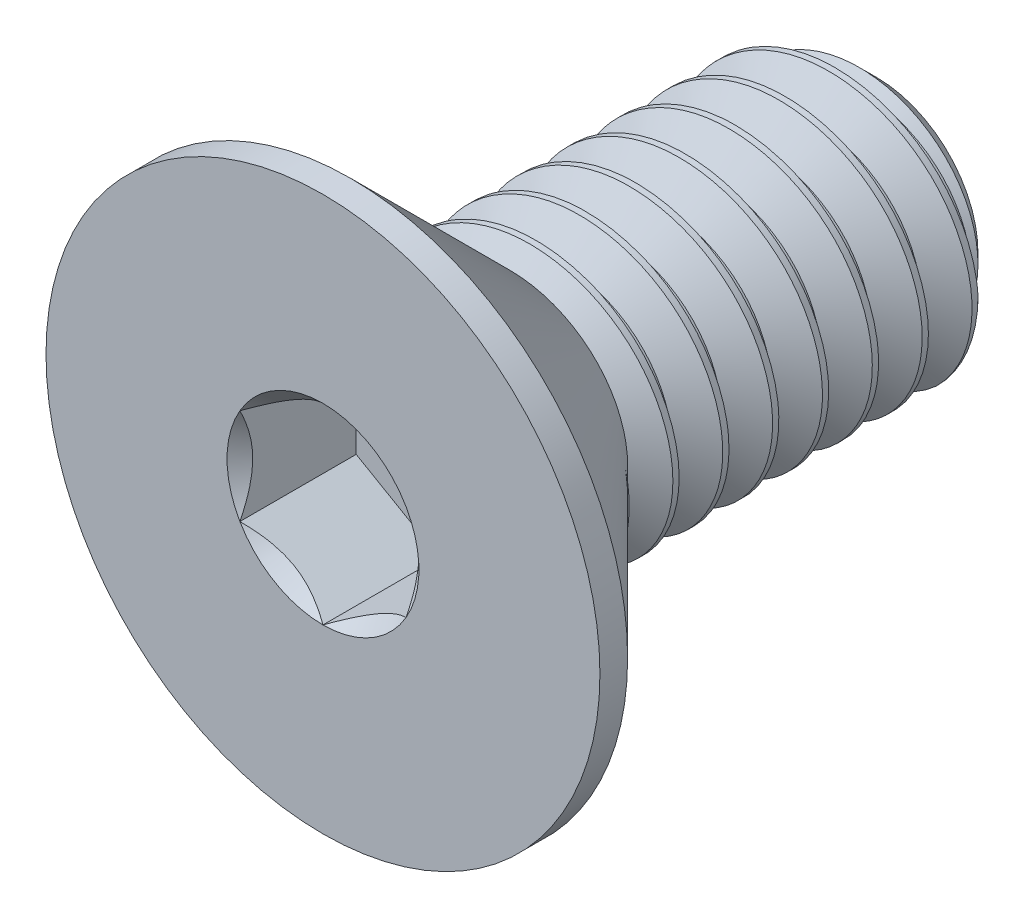
SolidWorks part; units mm, degrees
ref_plane "Front" through (0, 0, 0) normal (0, 0, 1) x (1, 0, 0)
ref_plane "Top" through (0, 0, 0) normal (0, 1, 0) x (1, 0, 0)
ref_plane "Right" through (0, 0, 0) normal (1, 0, 0) x (0, 0, -1)
sketch "Sketch1" plane through (0, 0, 0) normal (1, 0, 0) x (0, 0, -1)
  line L0 (0, 2.5) -> (0.25, 2.5) construction
  line L1 (0.25, 2.5) -> (1.5, 1.25) construction
  line L2 (0, 1.25) -> (5, 1.25)
  line L3 (5, 1.25) -> (5, 0)
  line L4 (5, 0) -> (0, 0)
  line L5 (0, 0) -> (0, 2.5) construction
  line L6 (0, 2.5) -> (0, -2.5) construction
  line L7 (5, 1.25) -> (5, -1.25) construction
  line L8 (0, -2.5) -> (0.25, -2.5) construction
  line L9 (0.25, -2.5) -> (1.5, -1.25) construction
  line L11 (0, 1.25) -> (0, 0)
  line L12 (1.5, 1.25) -> (1.5, 0) construction
  dimension "Head Ht" = 1.5
  dimension "Head Dia" = 5
  dimension "Dia" = 2.5
  dimension "Lg" = 5
  dimension "Head Angle" = 90
revolve "Revolve1" add sketch "Sketch1" angle 360 mid plane about L4
sketch "Sketch3" plane through (0, 0, -5) normal (0, 0, -1) x (-1, 0, 0)
  circle A0 centre (0, 0) radius 1.25
curve "Helix/Spiral1" pitch 0.45 height 5 radius 1.25 centre (0, 0, -5) axis (0, 0, 1) start towards (0, 1, 0)
sketch "Sketch2" plane through (0, 0, 0) normal (1, 0, 0) x (0, 0, -1)
  line L0 (5, 1.25) -> (5.3938, 1.25)
  line L1 (5.3938, 1.25) -> (5.225, 0.9577)
  line L2 (5.225, 0.9577) -> (5.1687, 0.9577)
  line L3 (5.1687, 0.9577) -> (5, 1.25)
  line L4 (5.0844, 1.1039) -> (5.3094, 1.1039) construction
  dimension "D1" = 60
  dimension "D2" = 0.0563
  dimension "D3" = 0.225
chamfer "Chamfer1" distance 0.3375 angle 45 1 edges at (0, 1.25, -5)
sweep "Cut-Sweep1" cut profiles "Sketch2" path "Helix/Spiral1" align with end faces yes
sketch "Sketch7" plane through (0, 0, 0) normal (1, 0, 0) x (0, 0, -1)
  line L0 (0, 2.5) -> (0.25, 2.5) construction
  line L1 (0.25, 2.5) -> (1.5, 1.25) construction
  line L2 (0, 2.5) -> (0.25, 2.5)
  line L3 (0.25, 2.5) -> (1.5, 1.25)
  line L4 (1.5, 1.25) -> (1.5, 0) construction
  line L5 (1.5, 1.25) -> (1.5, 0)
  line L7 (0, 0) -> (0, 2.5) construction
  line L8 (0, 0) -> (0, 2.5)
  line L9 (0, 0) -> (1.5, 0)
  line L10 (2.75, 0) -> (-2.75, 0) construction
revolve "Revolve2" add sketch "Sketch7" angle 360 mid plane about L9
ref_plane "Plane1" through (0, 0, -1.5) normal (0, 0, 1) x (1, 0, 0)
sketch "Sketch8" plane through (0, 0, -1.5) normal (0, 0, 1) x (1, 0, 0)
  circle A0 centre (0, 0) radius 1.25
extrude "Boss-Extrude1" add sketch "Sketch8" against normal through all draft 45
sketch "Sketch5" plane through (0, 0, 0) normal (0, 0, 1) x (1, 0, 0)
  line L1 (0.75, -0.433) -> (0.75, 0.433)
  line L2 (0.75, 0.433) -> (0, 0.866)
  line L3 (0, 0.866) -> (-0.75, 0.433)
  line L4 (-0.75, 0.433) -> (-0.75, -0.433)
  line L5 (-0.75, -0.433) -> (0, -0.866)
  line L6 (0, -0.866) -> (0.75, -0.433)
  circle A0 centre (0, 0) radius 0.75 construction
  dimension "Hex" = 1.5
extrude "Cut-Extrude2" cut sketch "Sketch5" against normal blind 1.05
sketch "Sketch6" plane through (0, 0, 0) normal (0, 0, 1) x (1, 0, 0)
  circle A0 centre (0, 0) radius 0.866
extrude "Cut-Extrude3" cut sketch "Sketch6" against normal blind 1.05 draft 45
sketch "Sketch9" [suppressed] plane through (0, 0, -1.5) normal (0, 0, 1) x (1, 0, 0)
  circle A1 centre (0, 0) radius 1.25
  circle A2 centre (0, 0) radius 1.25
  point P0 (0, 1.25)
  dimension "D1" = 0
extrude "Boss-Extrude2" [suppressed] add sketch "Sketch9" against normal offset from surface (3.5 mm away) 26 up to face at (0, 0.9125, -5)
fillet "Fillet1" [suppressed] radius 0.25
sketch "Sketch10" plane through (0, 0, 0) normal (1, 0, 0) x (0, 0, -1)
  line L0 (5, 1.25) -> (5, -1.25) construction
  point P0 (4.325, -1.25)
  dimension "D1" = 0.675
equation "\"D3@Helix/Spiral1\" = \"Lg@Sketch1\""
equation "\"D2@Sketch2\" = \"D4@Helix/Spiral1\" * .125"
equation "\"D3@Sketch2\" = \"D4@Helix/Spiral1\" * .5"
equation "\"D1@Chamfer1\" = \"D4@Helix/Spiral1\" * .75"
equation "\"D1@Cut-Extrude2\" = \"Head Ht@Sketch1\" * .7"
equation "\"D1@Sketch10\" = \"D4@Helix/Spiral1\" * 1.5"
equation "\"D1@Cut-Extrude3\" = \"D1@Cut-Extrude2\""
equation "\"D1@Fillet1\" = \"Dia@Sketch1\" * .1"
